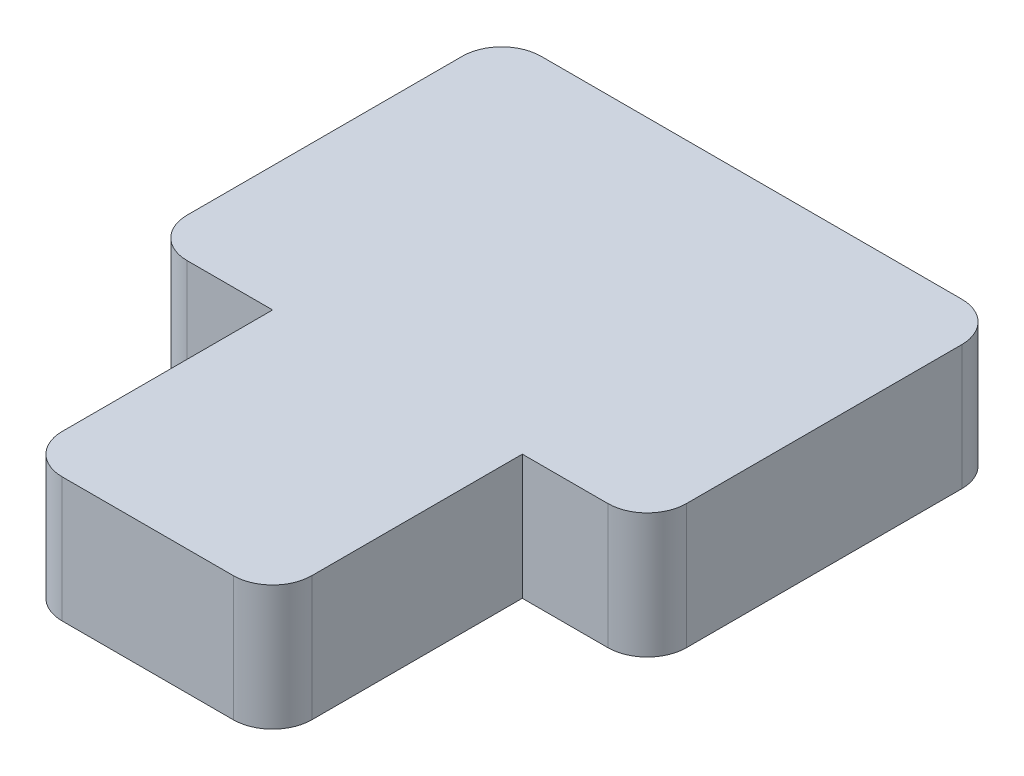
SolidWorks part; units mm, degrees
material "Beech"
ref_plane "Front Plane" through (0, 0, 0) normal (0, 0, 1) x (1, 0, 0)
ref_plane "Top Plane" through (0, 0, 0) normal (0, 1, 0) x (1, 0, 0)
ref_plane "Right Plane" through (0, 0, 0) normal (1, 0, 0) x (0, 0, -1)
sketch "Sketch1" plane through (0, 0, 0) normal (0, 1, 0) x (1, 0, 0)
  line L0 (0, 0) -> (6.35, 0)
  line L1 (0, 0) -> (0, 6.35)
  line L2 (6.35, 0) -> (6.35, 6.35)
  line L4 (-3.175, 15.35) -> (-3.175, 6.35)
  line L5 (-3.175, 15.35) -> (9.525, 15.35)
  line L6 (-3.175, 6.35) -> (0, 6.35)
  line L7 (9.525, 15.35) -> (9.525, 6.35)
  line L8 (6.35, 6.35) -> (9.525, 6.35)
  dimension "D1" = 6.35
  dimension "D2" = 6.35
  dimension "D3" = 12.7
  dimension "D4" = 9
extrude "MotorSupport_Extrude" add sketch "Sketch1" along normal blind 3.175
fillet "MotorSupport_BottomFillet" radius 1 6 edges at (0, 1.5875, 0) (6.35, 1.5875, 0) (-3.175, 1.5875, -15.35) (-3.175, 1.5875, -6.35) (9.525, 1.5875, -6.35) (9.525, 1.5875, -15.35)
equation "\"CageLeftBottomEdge\"=22.11mm"
equation "\"CageLeftTopEdge\"=22.11mm"
equation "\"CageRightBottomEdge\"=21.63mm"
equation "\"CageRightTopEdge\"=21.63mm"
equation "\"CageHeight\"=86.04mm"
equation "\"CageLength\"=73.76mm"
equation "\"CageTopScrewClearance\"=10mm"
equation "\"CageBottomScrewClearance\"=25mm"
equation "\"CageLeftTopDepth\"= 11.65mm"
equation "\"CageLeftBottomDepth\"=11.11mm"
equation "\"CageLeftTopHeight\"=8.56175mm"
equation "\"CageLeftBottomHeight\"=16mm"
equation "\"CageRightTopDepth\"= 11.05mm"
equation "\"CageRightBottomDepth\"=10.58mm"
equation "\"CageRightTopHeight\"=9.6mm"
equation "\"CageRightBottomHeight\"=15.49mm"
equation "\"CageLeftTopChannelDepth\"=2.41908mm"
equation "\"CageLeftBottomChannelDepth\"=2.588mm"
equation "\"CageLeftChannelHeight\"=11.7mm"
equation "\"CageRightTopChannelDepth\"=2.32mm"
equation "\"CageRightBottomChannelDepth\"=2.318mm"
equation "\"CageRightChannelHeight\"=10mm"
equation "\"CageChanRelHeight\"=23.99mm"
equation "\"CageChanRelDepth\"=5.492mm"
equation "\"CageChamberRadius\"=16.261mm"
equation "\"CageScrewDiameter\"=4.8mm"
equation "\"CageSetScrewDiameter\"=3.5mm"
equation "\"CageAxleRadius\"=6.639mm"
equation "\"CageAxleKeyHeight\"=1.619mm"
equation "\"CageAxleKeyWidth\"=2.662mm"
equation "\"CageHoseWindowWidth\"=16.29mm"
equation "\"CageHoseWindowHeight\"=26.5mm"
equation "\"CageHoseWindow-Edge\"=8.89mm"
equation "\"CageScrew-VerticalEdge\"=5.0mm"
equation "\"CageScrew-HorizontalEdge\"=7.5mm"
equation "\"CageScrew-HoseCornerScrewEdge\"=4.45mm"
equation "\"CageAxle-BottomEdge\"=56.05mm"
equation "\"CageAxle-FrontEdge\"=46.03mm"
equation "\"CageBackSetScrew-Axle\"=40mm"
equation "\"CageFrontSetScrew-Axle\"=22mm"
equation "\"CageVelocityWindow-BackEdge\"=34.8mm"
equation "\"CageVelocityWindow-BottomEdge\"=27.55mm"
equation "\"CageVelocityWindowHeight\"=22.29mm"
equation "\"CageVelocityWindowWidth\"=12.61mm"
equation "\"TriggerSlot-BottomEdge\"=6.35mm"
equation "\"TriggerSlot-FrontEdge\"=15mm"
equation "\"TriggerSlotSize\"=6.7mm"
equation "\"TriggerRackOffset\"=6mm"
equation "\"TriggerSlotSizeInt\"=.25in"
equation "\"MotorMountLegLength\"=.25in"
equation "\"GearOffset\"=.264907in"
equation "\"TriggerSlotSpacing\"=.25in"
equation "\"D1@Sketch1\"=\"TriggerSlotSizeInt\""
equation "\"D2@Sketch1\"=\"MotorMountLegLength\""
equation "\"D3@Sketch1\"=2*\"TriggerSlotSizeInt\""
equation "\"D4@Sketch1\"=1.5*\"TriggerRackOffset\""
equation "\"D1@MotorSupport_Extrude\"=.125in"
equation "\"TriggerMiniSlotWidth\"=3.5mm"
equation "\"TriggerRackWidth\"=6.5mm"
equation "\"pandiscradius\"=14in"
equation "\"towermaterialwidth\"=.25in"
equation "\"towerslotlength\"=.5in"
equation "\"towermarkerspace\"=5in"
equation "\"towerslothorizoffset\"=1in"
equation "\"towerslothorizspacing\"=2in"
equation "\"towerslotvertoffset\"=3in"
equation "\"towerslotvertspacing\"=1in"
equation "\"towerheight\"=12in"
equation "\"towerupslot\"=1in"
equation "\"toweraxle\"=.5in"
equation "\"stepperouterrad\"=10mm"
equation "\"stepperscrewsize\"=3.45mm"
equation "\"stepperscrewc2c\"=49.5mm"
equation "\"stepperdepthoffset\"=24mm"
equation "\"stepperhorizoffset\"=22.91mm"
equation "\"shaftslotOD\"=18.8mm"
equation "\"shaftslotID\"=13.28mm"
equation "\"shaftkeywidth\"=2.67mm"
equation "\"shaftkeydepth\"=1.8mm"
equation "\"shaftcollartotaldepth\"=12.5mm"
equation "\"shaftsquaredepth\"=6mm"
equation "\"shaftsetscrewsize\"=3.5mm"
equation "\"shaftkeytightdepth\"=1.85mm"
equation "\"shaftslottightID\"=12.78mm"
equation "\"shaftsetscrewoffset\"=9mm"
equation "\"cagecollartotaldepth\"=10mm"
equation "\"cagecollartotalwidth\"=35mm"
equation "\"cagecollarbasedepth\"=4mm"
equation "\"gearhubintdiam\"=30mm"
equation "\"gearhubintwid\"=15mm"
equation "\"towerspeedwidth\"=2in"
equation "\"towerspeedheight\"=8in"
equation "\"towerspeedgap\"=2in"
equation "\"stepperaxleflat\"=.037in"
equation "\"stepperaxlerad\"=0.11811024in"
equation "\"ajaxaxlesize\"=3.87mm"
equation "\"ajaxinnercut\"=2.3mm"
equation "\"ajaxwidth\"=6.1mm"
equation "\"ajaxdiametral\"=25.8854"
equation "\"ajaxcutoutdepth\"=2.3mm"
equation "\"ajax4020gap\"=29.5mm"
equation "\"ajax4010gap\"=24.5mm"
equation "\"ajax20hubbuffer\"=6.1mm"
equation "\"ajax20hubholeoffset\"=.19685in"
equation "\"ajax20hubholesize\"=.059055in"
equation "\"ajax20cutoutint\"=13.4mm"
equation "\"ajax40hubholesize\"=7.21mm"
equation "\"ajax40hubholeoffset\"=10mm"
equation "\"ajax40hubbuffer\"=8.9mm"
equation "\"ajax40cutoutint\"=32.6mm"
equation "\"bearingpandiscrad\"=6.8in"
equation "\"bearingpandiscang\"=48.75deg"
equation "\"bearingclearholedist\"=4.7345in"
equation "\"bearingclearholesize\"=.5in"
equation "\"bearingclearholeang\"=22.5deg"
equation "\"bearingmountholedist\"=4.25in"
equation "\"bearingwirehole\"=1.5in"
equation "\"no6diam\"=.146in"
equation "\"shortconangle\"=20deg"
equation "\"shortconlen\"=.875in"
equation "\"longconlen\"=1.25in"
equation "\"longconangle\"=15deg"
